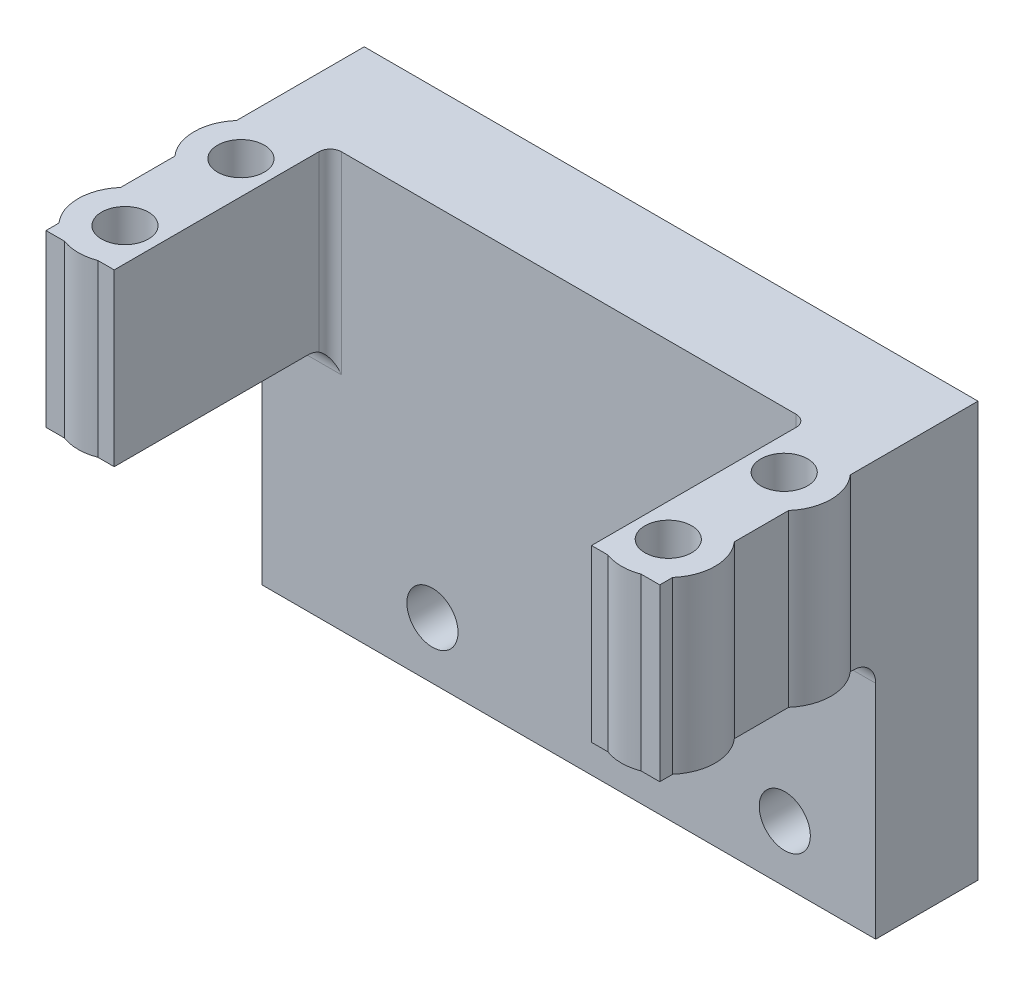
SolidWorks part; units mm, degrees
ref_plane "Front Plane" through (0, 0, 0) normal (0, 0, 1) x (1, 0, 0)
ref_plane "Top Plane" through (0, 0, 0) normal (0, 1, 0) x (1, 0, 0)
ref_plane "Right Plane" through (0, 0, 0) normal (1, 0, 0) x (0, 0, -1)
sketch "Sketch1" plane through (0, 0, 0) normal (0, 0, 1) x (1, 0, 0)
  line L1 (-27, 13.25) -> (27, 13.25)
  line L2 (-27, 13.25) -> (-27, -13.25)
  line L3 (-27, -13.25) -> (27, -13.25)
  line L4 (27, 13.25) -> (27, -13.25)
  dimension "D1" = 54
  dimension "D2" = 27
  dimension "D3" = 26.5
  dimension "D4" = 13.25
extrude "Boss-Extrude1" add sketch "Sketch1" along normal blind 9
sketch "Sketch2" plane through (0, 0, 9) normal (0, 0, 1) x (1, 0, 0)
  line L1 (27, 13.25) -> (21, 13.25)
  line L2 (27, 13.25) -> (27, -1.75)
  line L3 (27, -1.75) -> (21, -1.75)
  line L4 (21, 13.25) -> (21, -1.75)
  dimension "D1" = 6
  dimension "D2" = 15
extrude "Boss-Extrude2" add sketch "Sketch2" along normal blind 19
sketch "Sketch4" plane through (0, 13.25, 0) normal (0, 1, 0) x (1, 0, 0)
  line L0 (21, -28) -> (21, -9) construction
  line L1 (27, -28) -> (21, -28) construction
  circle A0 centre (23.9, -13.9495) radius 2.06
  circle A1 centre (23.9, -24.1495) radius 2.06
  dimension "D1" = 4.12
  dimension "D2" = 4.12
  dimension "D3" = 2.9
  dimension "D4" = 14.0505
  dimension "D5" = 10.2
extrude "Cut-Extrude1" cut sketch "Sketch4" against normal blind 19
sketch "Sketch5" plane through (0, 13.25, 0) normal (0, 1, 0) x (1, 0, 0)
  line L0 (21, -28) -> (21, -9) construction
  line L1 (21, -27.076) -> (21, -21.223)
  line L2 (21, -16.876) -> (21, -11.023)
  circle A0 centre (23.9, -13.9495) radius 2.06
  arc A1 (21, -16.876) -> (21, -11.023) centre (23.9, -13.9495) ccw
  circle A2 centre (23.9, -24.1495) radius 2.06
  arc A3 (21, -27.076) -> (21, -21.223) centre (23.9, -24.1495) ccw
  dimension "D1" = 4.12
  dimension "D2" = 4.12
  dimension "D3" = 8.24
  dimension "D4" = 8.24
extrude "Boss-Extrude3" add sketch "Sketch5" against normal blind 15
sketch "Sketch8" plane through (0, 0, 9) normal (0, 0, 1) x (1, 0, 0)
  line L0 (27, -13.25) -> (27, -1.75) construction
  line L1 (-27, -13.25) -> (27, -13.25)
  line L2 (-27, -13.25) -> (-27, -23.25)
  line L3 (-27, -23.25) -> (27, -23.25)
  line L4 (27, -13.25) -> (27, -23.25)
  dimension "D1" = 10
extrude "Boss-Extrude5" add sketch "Sketch8" against normal through all
sketch "Sketch9" plane through (0, 0, 9) normal (0, 0, 1) x (1, 0, 0)
  line L0 (27, -23.25) -> (27, -1.75) construction
  line L1 (-27, -23.25) -> (27, -23.25) construction
  line L2 (-27, 13.25) -> (-27, -23.25) construction
  circle A0 centre (19, -18.25) radius 2.25
  circle A1 centre (-12, -18.25) radius 2.25
  dimension "D1" = 4.5
  dimension "D2" = 4.5
  dimension "D3" = 8
  dimension "D4" = 5
  dimension "D5" = 15
extrude "Cut-Extrude3" cut sketch "Sketch9" against normal blind 15
ref_plane "Plane1" through (0, 0, 0) normal (-1, 0, 0) x (0, 0, 1)
mirror "Mirror1" about plane through (0, 0, 0) normal (-1, 0, 0) of "Cut-Extrude1", "Boss-Extrude3", "Boss-Extrude2", "Boss-Extrude1"
fillet "Fillet1" radius 2 2 edges at (24, -1.75, 9) (-24, -1.75, 9)
fillet "Fillet2" radius 1 2 edges at (-21, 4.75, 9) (21, 4.75, 9)
